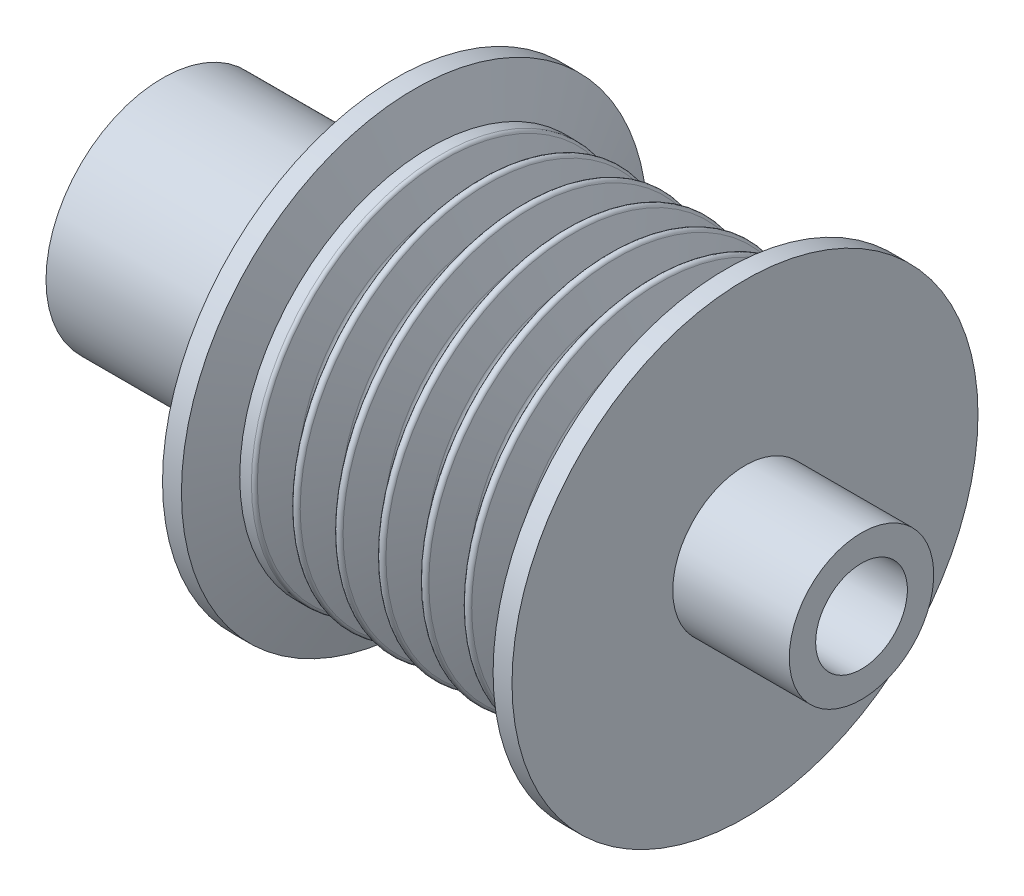
SolidWorks part; units mm, degrees
material "6061-T6 (SS)"
ref_plane "Front Plane" through (0, 0, 0) normal (0, 0, 1) x (1, 0, 0)
ref_plane "Top Plane" through (0, 0, 0) normal (0, 1, 0) x (1, 0, 0)
ref_plane "Right Plane" through (0, 0, 0) normal (1, 0, 0) x (0, 0, -1)
sketch "Sketch1" plane through (0, 0, 0) normal (0, 0, 1) x (1, 0, 0)
  line L0 (0, 0) -> (0, 2.5) construction
  line L1 (0, 2.5) -> (38.1, 2.5)
  line L2 (31.75, 3.937) -> (31.75, 12.7)
  line L3 (31.75, 12.7) -> (12.7, 12.7)
  line L4 (12.7, 12.7) -> (12.7, 6.35)
  line L5 (0, 0) -> (13.5959, 0) construction
  line L6 (31.75, 3.937) -> (38.1, 3.937)
  line L7 (38.1, 3.937) -> (38.1, 2.5)
  line L8 (12.7, 6.35) -> (0, 6.35)
  line L9 (0, 6.35) -> (0, 2.5)
  point P11 (6.4406, 12.7)
  point P13 (0, 2.9071)
  dimension "D1" = 25.4
  dimension "D2" = 5
  dimension "D3" = 19.05
  dimension "D4" = 7.874
  dimension "D5" = 6.35
  dimension "D6" = 12.7
  dimension "D7" = 12.7
revolve "Revolve1" add sketch "Sketch1" angle 360 about L5
sketch "Sketch2" plane through (0, 0, 0) normal (0, 0, 1) x (1, 0, 0)
  line L0 (26.8986, 12.7) -> (26.8986, 10.3699)
  line L2 (27.0895, 10.2362) -> (27.6851, 8.5999)
  line L3 (28.4489, 8.5999) -> (29.0445, 10.2362)
  line L4 (29.2354, 10.3699) -> (29.2354, 12.7)
  line L5 (29.2354, 12.7) -> (26.8986, 12.7)
  line L6 (26.8986, 11.43) -> (29.2354, 11.43) construction
  line L7 (0, 0) -> (24.4755, 0) construction
  line L8 (27.0895, 10.2362) -> (29.0445, 10.2362) construction
  line L9 (26.8986, 12.7) -> (24.5618, 12.7) construction
  line L10 (31.75, 12.7) -> (12.7, 12.7) construction
  line L11 (24.5618, 12.7) -> (22.225, 12.7) construction
  arc A0 (26.8986, 10.3699) -> (27.0895, 10.2362) centre (26.8986, 10.1667) cw
  arc A1 (27.6851, 8.5999) -> (28.4489, 8.5999) centre (28.067, 8.7389) ccw
  arc A2 (29.0445, 10.2362) -> (29.2354, 10.3699) centre (29.2354, 10.1667) cw
  dimension "D1" = 0.4064
  dimension "D5" = 0.2032
  dimension "D2" = 2.3368
  dimension "D3" = 11.43
  dimension "D4" = 1.1938
  dimension "D6" = 40
revolve "Cut-Revolve1" cut sketch "Sketch2" angle 360 about L7
pattern_linear "LPattern1" count 6 spacing 2.3368 along (-1, 0, 0) of "Cut-Revolve1"
sketch "Sketch3" plane through (0, 0, 0) normal (0, 0, 1) x (1, 0, 0)
  line L0 (29.2354, 12.7) -> (30.7185, 12.7)
  line L1 (31.75, 12.7) -> (29.2354, 12.7) construction
  line L2 (30.7185, 12.7) -> (29.8704, 10.3699)
  line L3 (29.8704, 10.3699) -> (29.2354, 10.3699)
  line L4 (29.2354, 12.7) -> (29.2354, -12.7) construction
  line L5 (29.2354, 10.3699) -> (29.2354, 12.7)
  line L6 (29.2354, 10.3699) -> (29.2354, -10.3699) construction
  line L7 (28.067, 8.3325) -> (28.067, 11.4458) construction
  line L8 (22.225, 10.3699) -> (22.225, 14.7012) construction
  line L9 (15.2146, 10.3699) -> (15.2146, 12.7)
  line L10 (14.5796, 10.3699) -> (15.2146, 10.3699)
  line L11 (13.7315, 12.7) -> (14.5796, 10.3699)
  line L12 (15.2146, 12.7) -> (13.7315, 12.7)
  line L13 (0, 0) -> (26.9583, 0) construction
  arc A0 (27.6851, 8.5999) -> (28.4489, 8.5999) centre (28.067, 8.7389) ccw construction
  arc A1 (22.4159, 10.2362) -> (22.0341, 10.2362) centre (22.225, 10.1667) ccw construction
  dimension "D1" = 1.8034
  dimension "D2" = 20
revolve "Cut-Revolve2" cut sketch "Sketch3" angle 360 about L13
ref_plane "Plane1" through (0, 6.35, 0) normal (0, 1, 0) x (1, 0, 0)
sketch "Sketch6" plane through (0, 6.35, 0) normal (0, 1, 0) x (1, 0, 0)
  line L0 (12.7, 6.35) -> (12.7, -6.35) construction
  line L1 (10.16, 0) -> (0, 0) construction
  circle A0 centre (10.16, 0) radius 2.54 construction
  point P0 (10.16, 0)
  dimension "D1" = 5.08
hole_wizard "#10-24 Tapped Hole1" positions "Sketch6" profile "Sketch5" tap size "#10-24" standard "ANSI Inch" end condition up to next
sketch "Sketch5" plane through (10.16, 6.35, 0) normal (1, 0, 0) x (0, 0, 1)
  line L0 (0, 0) -> (0, 3.85)
  line L1 (0, 3.85) -> (1.8986, 3.85)
  line L2 (1.8986, 3.85) -> (1.8986, 0)
  line L5 (1.8986, 0) -> (0, 0)
  line L11 (0, -6.35) -> (0, 107.95) construction
  dimension "Thru Tap Drill Dia." = 3.7973
  dimension "Thru Tap Drill Depth" = 3.85
equation "\"D2@Sketch1\"=5mm"
equation "\"D3@Sketch2\"=0.9in/2"
equation "\"D4@Sketch2\"=0.094in/2"
